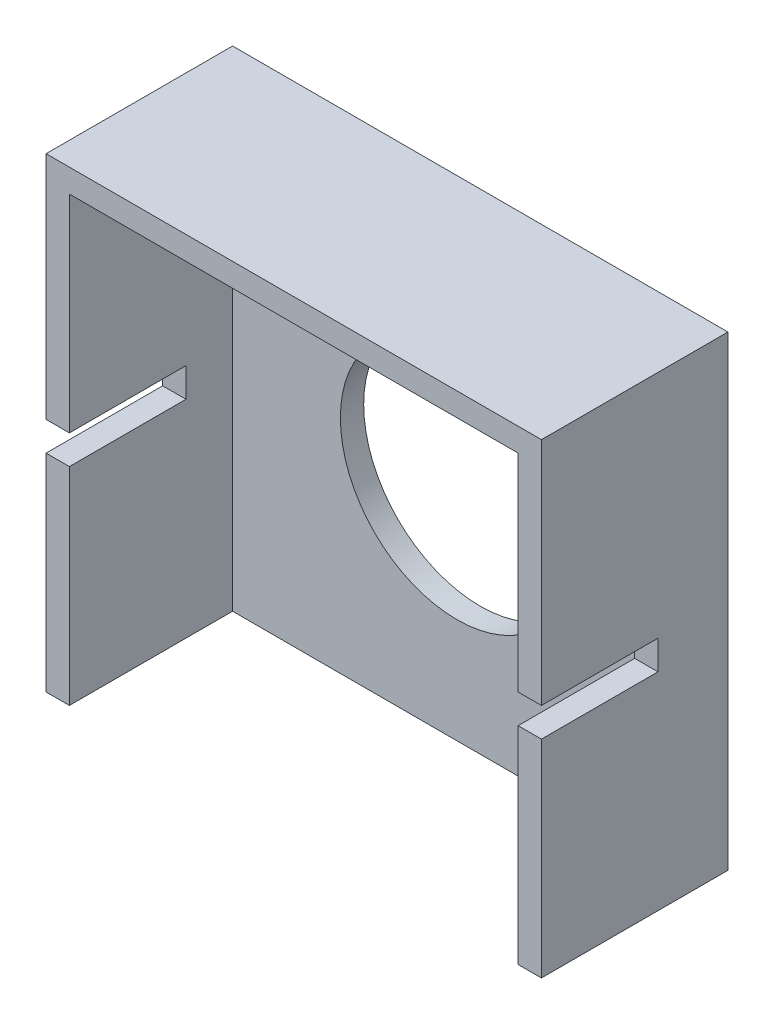
SolidWorks part; units mm, degrees
ref_plane "Front Plane" through (0, 0, 0) normal (0, 0, 1) x (1, 0, 0)
ref_plane "Top Plane" through (0, 0, 0) normal (0, 1, 0) x (1, 0, 0)
ref_plane "Right Plane" through (0, 0, 0) normal (1, 0, 0) x (0, 0, -1)
sketch "Sketch1" plane through (0, 0, 0) normal (0, 0, 1) x (1, 0, 0)
  line L1 (-19.25, 19) -> (19.25, 19)
  line L2 (-19.25, 19) -> (-19.25, -19)
  line L3 (-19.25, -19) -> (19.25, -19)
  line L4 (19.25, 19) -> (19.25, -19)
  line L5 (-19.25, 19) -> (19.25, -19) construction
  line L6 (-19.25, -19) -> (19.25, 19) construction
  circle A0 centre (0, 0) radius 10
  point P0 (0, 0)
  dimension "D3" = 20
  dimension "D1" = 38.5
  dimension "D2" = 38
extrude "Boss-Extrude1" add sketch "Sketch1" along normal blind 2 contours L1 L2 L3 | L1 L3 A0 | L1 L3 L4 | L1 region at (0, 18.4591, 0)
sketch "Sketch2" plane through (0, 0, 2) normal (0, 0, 1) x (1, 0, 0)
  line L0 (-19.25, -19) -> (-21.25, -19)
  line L1 (-21.25, -19) -> (-21.25, 21)
  line L2 (-21.25, 21) -> (21.25, 21)
  line L4 (19.25, -19) -> (21.25, -19)
  line L6 (19.25, -19) -> (19.25, 19)
  line L7 (19.25, 19) -> (-19.25, 19)
  line L8 (0, 40.5) -> (0, -19) construction
  line L9 (-19.25, 19) -> (-19.25, -19)
  line L10 (-19.25, -19) -> (19.25, -19) construction
  line L11 (-19.25, -19) -> (19.25, -19)
  line L12 (19.25, -19) -> (19.25, 19)
  line L13 (19.25, 19) -> (-19.25, 19)
  line L14 (-19.25, 19) -> (-19.25, -19)
  line L15 (-19.25, -19) -> (19.25, -19)
  line L16 (21.25, -19) -> (21.25, 21)
  point P10 (0, 21)
  line M17 (19.25, -19) -> (19.25, 19)
  line M18 (19.25, 19) -> (-19.25, 19)
  line M22 (19.25, 19) -> (-19.25, 19)
  line M23 (-19.25, 19) -> (-19.25, -19)
  dimension "D1" = 0
  dimension "D2" = 2
  dimension "D3" = 2
extrude "Boss-Extrude2" add sketch "Sketch2" along normal blind 14 and the other way up to surface (2 mm away) contours L8 M23 M22 | L8 M18 M17 region at (-20.25, -18.4164, 2) other way up to face at (10, 0, 0)
sketch "Sketch3" plane through (-19.25, 0, 0) normal (1, 0, 0) x (0, 0, -1)
  line L0 (-2, 0) -> (-16, 0) construction
  line L1 (-2, 19) -> (-2, -19) construction
  line L2 (-16, 19) -> (-16, -19) construction
  line L3 (-16, 1.25) -> (-9, 0) construction
  line L4 (-6, 1.25) -> (-16, 1.25)
  line L5 (-6, 1.25) -> (-6, -1.25)
  line L6 (-6, -1.25) -> (-16, -1.25)
  line L7 (-16, 1.25) -> (-16, -1.25)
  line L8 (-9, 0) -> (-16, -1.25) construction
  dimension "D1" = 2.5
  dimension "D2" = 4
extrude "Cut-Extrude1" cut sketch "Sketch3" against normal up to next
ref_plane "Plane1" through (0, 0, 0) normal (1, 0, 0) x (0, 0, -1)
mirror "Mirror1" about plane through (0, 0, 0) normal (1, 0, 0) of "Cut-Extrude1"
